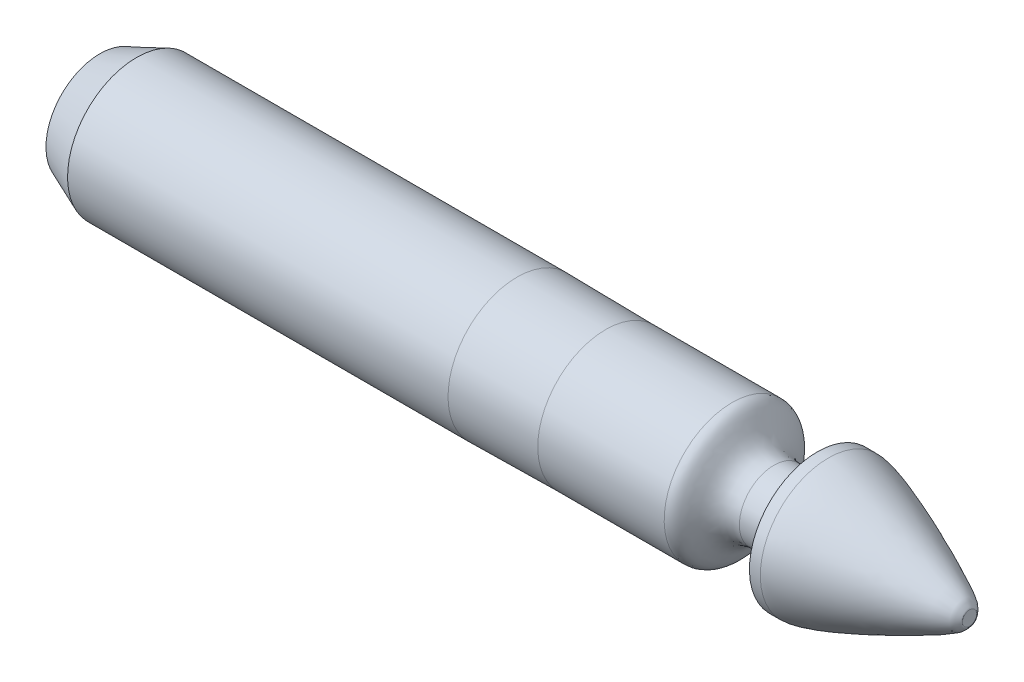
SolidWorks part; units mm, degrees
material "Stainless Steel (ferritic)"
ref_plane "Front" through (0, 0, 0) normal (0, 0, 1) x (1, 0, 0)
ref_plane "Top" through (0, 0, 0) normal (0, 1, 0) x (1, 0, 0)
ref_plane "Right" through (0, 0, 0) normal (1, 0, 0) x (0, 0, -1)
sketch "body_sketch" plane through (0, 0, 0) normal (0, 0, 1) x (1, 0, 0)
  line L1 (-16.7357, 3.1242) -> (-10.9218, 3.1242)
  line L2 (-38.31, 3.175) -> (-20.8111, 3.175)
  line L3 (-19.1074, 3.175) -> (-22.5343, 3.175) construction
  line L4 (-6.5, 3.1242) -> (-7, 3.1242)
  line L5 (-15.6683, 3.1242) -> (-17.809, 3.1242) construction
  line L6 (-40, 0) -> (-40, 2.4778)
  line L7 (-40, 2.4778) -> (-38.31, 3.175)
  line L9 (-7, 3.1242) -> (-7, 1.5875)
  line L10 (-7, 1.5875) -> (-9, 1.5875)
  line L13 (14.3233, 1.5875) -> (12.3233, 1.5875) construction
  line L14 (-10.9218, 3.1242) -> (-7, 3.1242) construction
  line L15 (0, 0) -> (-40, 0)
  line L17 (0, 0.3278) -> (0, 0)
  spline S0 degree 3 poles (-6.5, 3.1242) (-5.4841, 3.1242) (-0.4543, 0.8976) (-0.0546, 0.4238) (0, 0.3773) (0, 0.3278) knots 0 0 0 0 0.586138 0.686138 1 1 1 1
  spline S1 degree 3 poles (-10.9218, 3.1242) (-10.1654, 3.1242) (-10.25, 1.5875) (-9, 1.5875) knots 0 0 0 0 1 1 1 1
  spline S2 degree 3 poles (-20.8111, 3.175) (-19.3832, 3.175) (-18.0736, 3.1242) (-16.7357, 3.1242) knots 0 0 0 0 1 1 1 1
  point P5 (0, 0)
  point P8 (0, 0)
  point P11 (0, 0)
  point P12 (-10.2981, 3.175)
  point P15 (-7, 3.175)
  point P16 (0, 0)
  point P17 (0, 0)
  point P18 (-10.7335, 2.8403)
  point P21 (0, 0)
  point P24 (0, 0)
  dimension "D1" = 3.175
  dimension "D2" = 0.5
  dimension "D3" = 2
  dimension "D4" = 1.5875
  dimension "D5" = 40
  dimension "D6" = 7
  dimension "D7" = 3.1242
revolve "body" add sketch "body_sketch" angle 360 about L15
sketch "minimum_diameter" plane through (0, 0, 0) normal (1, 0, 0) x (0, 0, -1)
  circle A0 centre (0, 0) radius 1.5875 construction
  circle A2 centre (0, 0) radius 1.5875 construction
